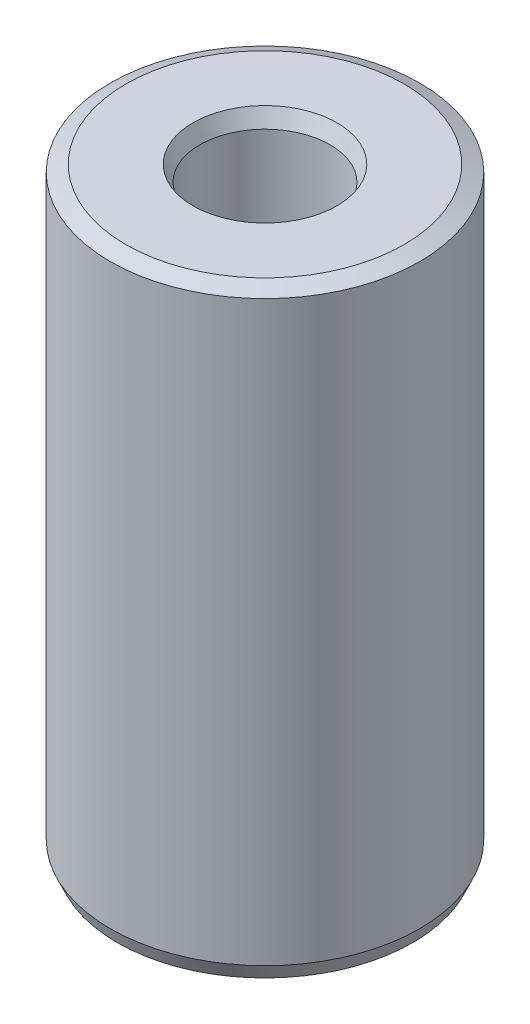
SolidWorks part; units mm, degrees
ref_plane "Front Plane" through (0, 0, 0) normal (0, 0, 1) x (1, 0, 0)
ref_plane "Top Plane" through (0, 0, 0) normal (0, 1, 0) x (1, 0, 0)
ref_plane "Right Plane" through (0, 0, 0) normal (1, 0, 0) x (0, 0, -1)
sketch "Sketch1" plane through (0, 0, 0) normal (0, 1, 0) x (1, 0, 0)
  circle A0 centre (0, 0) radius 55
  dimension "SLEEVE_OD" = 110
extrude "Boss-Extrude1" add sketch "Sketch1" along normal blind 213.3984
sketch "Sketch2" plane through (0, 0, 0) normal (0, 1, 0) x (1, 0, 0)
  circle A0 centre (0, 0) radius 23.1301
  dimension "BORE_D" = 46.2602
extrude "Cut-Extrude1" cut sketch "Sketch2" along normal through all
chamfer "Chamfer1" distance 2.4662 angle 65.965 4 edges at (0, 213.3984, 23.1301) (0, 0, 23.1301) (0, 0, 55) (0, 213.3984, 55) first distance on face at (0, 213.3984, 23.1301) first distance on face at (0, 0, 23.1301) first distance on face at (0, 213.3984, 55)
